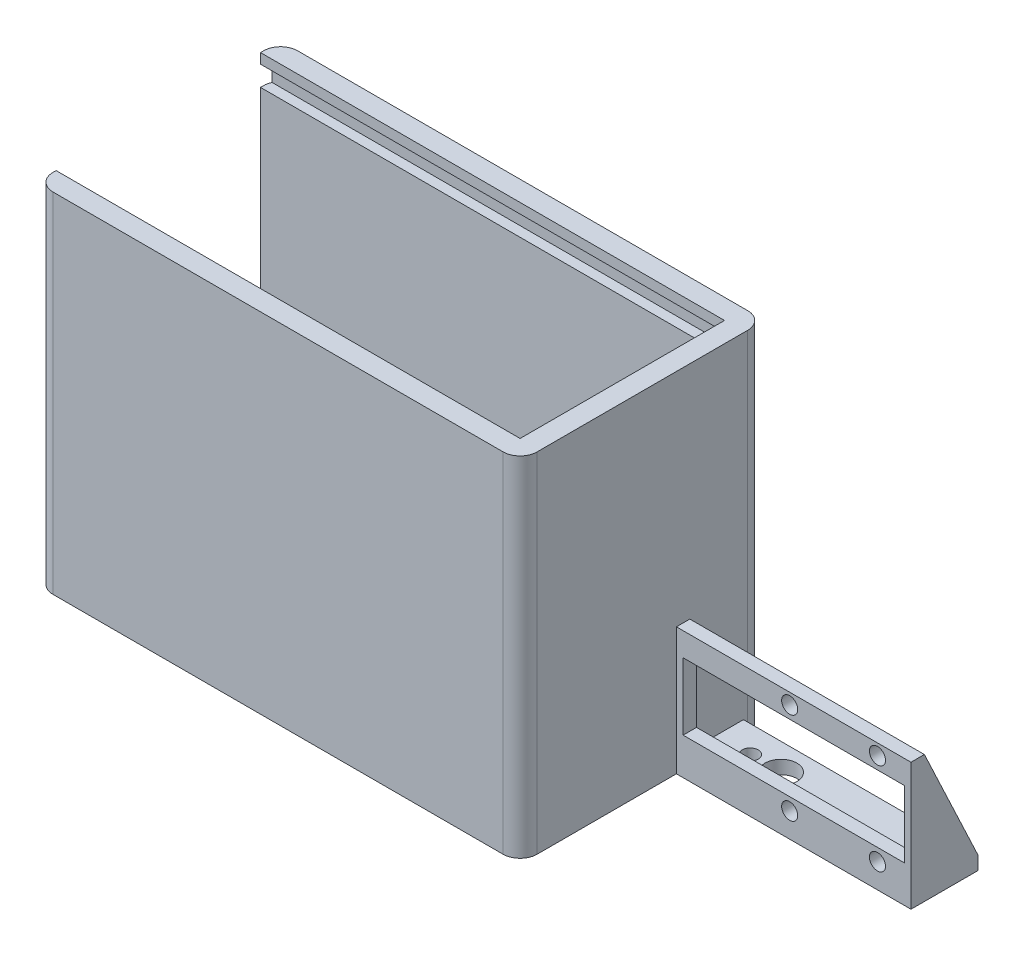
SolidWorks part; units mm, degrees
ref_plane "Front Plane" through (0, 0, 0) normal (0, 0, 1) x (1, 0, 0)
ref_plane "Top Plane" through (0, 0, 0) normal (0, 1, 0) x (1, 0, 0)
ref_plane "Right Plane" through (0, 0, 0) normal (1, 0, 0) x (0, 0, -1)
sketch "Sketch1" plane through (0, 0, 0) normal (0, 0, 1) x (1, 0, 0)
  line L1 (0, 0) -> (35, 0)
  line L2 (0, 0) -> (0, 17)
  line L3 (0, 17) -> (35, 17)
  line L4 (35, 0) -> (35, 17)
  line L5 (16.9, 15.35) -> (30, 15.35) construction
  line L6 (16.9, 15.35) -> (16.9, 1.65) construction
  line L7 (16.9, 1.65) -> (30, 1.65) construction
  line L8 (30, 15.35) -> (30, 1.65) construction
  point P9 (35, 8.5)
  point P10 (30, 8.5)
  dimension "D3" = 13.1
  dimension "D1" = 35
  dimension "D2" = 17
  dimension "D4" = 13.7
  dimension "D5" = 16.9
extrude "Boss-Extrude1" add sketch "Sketch1" along normal blind 2
hole_wizard "M2 Clearance Hole1" positions "Sketch4" profile "Sketch3" hole size "M2" standard "ANSI Metric" end condition through all
sketch "Sketch4" plane through (0, 0, 2) normal (0, 0, 1) x (1, 0, 0)
  point P0 (16.9, 15.35)
  point P3 (30, 15.35)
  point P6 (30, 1.65)
  point P9 (16.9, 1.65)
sketch "Sketch3" plane through (16.9, 15.35, 2) normal (1, 0, 0) x (0, -1, 0)
  line L0 (0, 0) -> (0, 2)
  line L1 (0, 2) -> (1.2, 2)
  line L2 (1.2, 2) -> (1.2, 0)
  line L5 (1.2, 0) -> (0, 0)
  line L11 (0, -6.35) -> (0, 107.95) construction
  dimension "Thru Hole Dia." = 2.4
  dimension "Thru Hole Depth" = 2
sketch "Sketch6" plane through (0, 0, 0) normal (0, -1, 0) x (1, 0, 0)
  line L0 (35, 2) -> (35, 0) construction
  line L1 (0, 2) -> (35, 2)
  line L2 (0, 2) -> (0, -8)
  line L3 (0, -8) -> (35, -8)
  line L4 (35, 2) -> (35, -8)
  dimension "D1" = 10
extrude "Boss-Extrude2" add sketch "Sketch6" along normal blind 2
sketch "Sketch7" plane through (0, 0, 2) normal (0, 0, 1) x (1, 0, 0)
  line L0 (0, 8.5) -> (35, 8.5) construction
  line L1 (0, 0) -> (0, 17) construction
  line L2 (35, 0) -> (35, 17) construction
  line L3 (0, 17) -> (35, 17) construction
  line L4 (1, 13.5) -> (34, 13.5)
  line L5 (1, 13.5) -> (1, 3.5)
  line L6 (1, 3.5) -> (34, 3.5)
  line L7 (34, 13.5) -> (34, 3.5)
  point P10 (0, 0)
  point P13 (17.5, 17)
  point P14 (17.5, 13.5)
  point P15 (1, 8.5)
  dimension "D1" = 10
  dimension "D2" = 33
extrude "Cut-Extrude1" cut sketch "Sketch7" against normal through all
sketch "Sketch8" plane through (0, 0, 0) normal (0, 1, 0) x (1, 0, 0)
  line L0 (5, 4) -> (30, 4) construction
  line L3 (0, 0) -> (0, 8) construction
  line L4 (0, 8) -> (35, 8) construction
  point P5 (17.5, 8)
  point P6 (5, 4)
  point P7 (30, 4)
  point P8 (17.5, 4)
  point P12 (0, 0)
  point P13 (0, 4)
  dimension "D1" = 25
hole_wizard "M2 Clearance Hole2" positions "Sketch8" profile "Sketch9" hole size "M2" standard "ANSI Metric" end condition through all
sketch "Sketch9" plane through (30, 0, -4) normal (1, 0, 0) x (0, 0, 1)
  line L0 (0, 0) -> (0, 2)
  line L1 (0, 2) -> (1.2, 2)
  line L2 (1.2, 2) -> (1.2, 0)
  line L5 (1.2, 0) -> (0, 0)
  line L11 (0, -6.35) -> (0, 107.95) construction
  dimension "Thru Hole Dia." = 2.4
  dimension "Thru Hole Depth" = 2
sketch "Sketch10" plane through (0, 0, 0) normal (-1, 0, 0) x (0, 0, 1)
  line L1 (-11.175, -2) -> (25.325, -2)
  line L2 (-11.175, -2) -> (-11.175, 0)
  line L3 (-11.175, 0) -> (25.325, 0)
  line L4 (25.325, -2) -> (25.325, 0)
  line L5 (0, 0) -> (-8, 0) construction
  line L7 (-11.175, -2) -> (25.325, -2) construction
  point P10 (7.075, -2)
  point P13 (7.075, -2)
  dimension "D1" = 36.5
extrude "Boss-Extrude3" add sketch "Sketch10" along normal up to surface (72.2375 mm away)
sketch "Sketch11" plane through (0, 0, 0) normal (0, 1, 0) x (1, 0, 0)
  line L0 (0, -25.325) -> (0, -2) construction
  line L1 (0, -25.325) -> (-72.2375, -25.325)
  line L2 (0, -25.325) -> (0, 11.175)
  line L3 (0, 11.175) -> (-72.2375, 11.175)
  line L4 (-72.2375, -25.325) -> (-72.2375, -22.325)
  line L5 (-72.2375, -25.325) -> (0, -25.325) construction
  line L6 (-3, -22.325) -> (-3, 8.175)
  line L7 (-3, 8.175) -> (-69.2375, 8.175)
  line L9 (-3, -22.325) -> (-69.2375, -22.325)
  line L10 (-69.2375, -22.325) -> (-72.2375, -22.325)
  line L11 (-69.2375, 8.175) -> (-72.2375, 8.175)
  line L12 (-72.2375, 8.175) -> (-72.2375, 11.175)
  line L13 (-69.2375, -22.325) -> (-69.2375, 8.175) construction
  line L14 (-72.2375, -25.325) -> (-72.2375, 11.175) construction
  dimension "D1" = 3
extrude "Boss-Extrude4" add sketch "Sketch11" along normal blind 50
sketch "Sketch12" plane through (-72.2375, 0, 0) normal (-1, 0, 0) x (0, 0, 1)
  line L0 (-11.175, -2) -> (-11.175, 50) construction
  line L1 (23.825, 48.5) -> (22.325, 48.5)
  line L2 (23.825, 48.5) -> (23.825, 45.5)
  line L3 (23.825, 45.5) -> (22.325, 45.5)
  line L4 (-9.675, 48.5) -> (-9.675, 45.5)
  line L5 (25.325, 50) -> (25.325, -2) construction
  line L7 (22.325, 50) -> (22.325, 0) construction
  line L9 (-8.175, 48.5) -> (-9.675, 48.5)
  line L10 (-8.175, 45.5) -> (-9.675, 45.5)
  line L11 (22.325, 50) -> (25.325, 50) construction
  line L13 (-8.175, 48.5) -> (22.325, 48.5)
  line L14 (-8.175, 45.5) -> (22.325, 45.5)
  line L15 (-8.175, 50) -> (-8.175, 0) construction
  line L16 (-8.175, 50) -> (-8.175, 0) construction
  point P14 (23.075, 45.5)
  point P17 (0, 0)
  point P20 (0, 0)
  dimension "D1" = 1.5
  dimension "D2" = 1.5
  dimension "D3" = 3
  dimension "D4" = 4.5
extrude "Cut-Extrude2" cut sketch "Sketch12" against normal up to surface (69.2375 mm away) up to face at (-3, 25, 7.075)
sketch "Sketch14" plane through (35, 0, 0) normal (1, 0, 0) x (0, 0, -1)
  line L0 (8, 0) -> (0, 17)
  line L1 (0, 17) -> (0, 0)
  line L2 (0, 0) -> (8, 0)
  point P3 (8.9242, 0)
extrude "Boss-Extrude5" add sketch "Sketch14" against normal blind 1
fillet "Fillet1" radius 2.54 4 edges at (0, 24, 25.325) (0, 24, -11.175) (-72.2375, 24, -11.175) (-72.2375, 24, 25.325)
sketch "Sketch15" plane through (0, -2, 0) normal (0, -1, 0) x (1, 0, 0)
  circle A0 centre (9.6, -4) radius 2.3813 construction
  circle A1 centre (9.6, -4) radius 2.3813
extrude "Cut-Extrude3" cut sketch "Sketch15" against normal through all
equation "\"D1@Sketch10\"=26.5+6+4"
